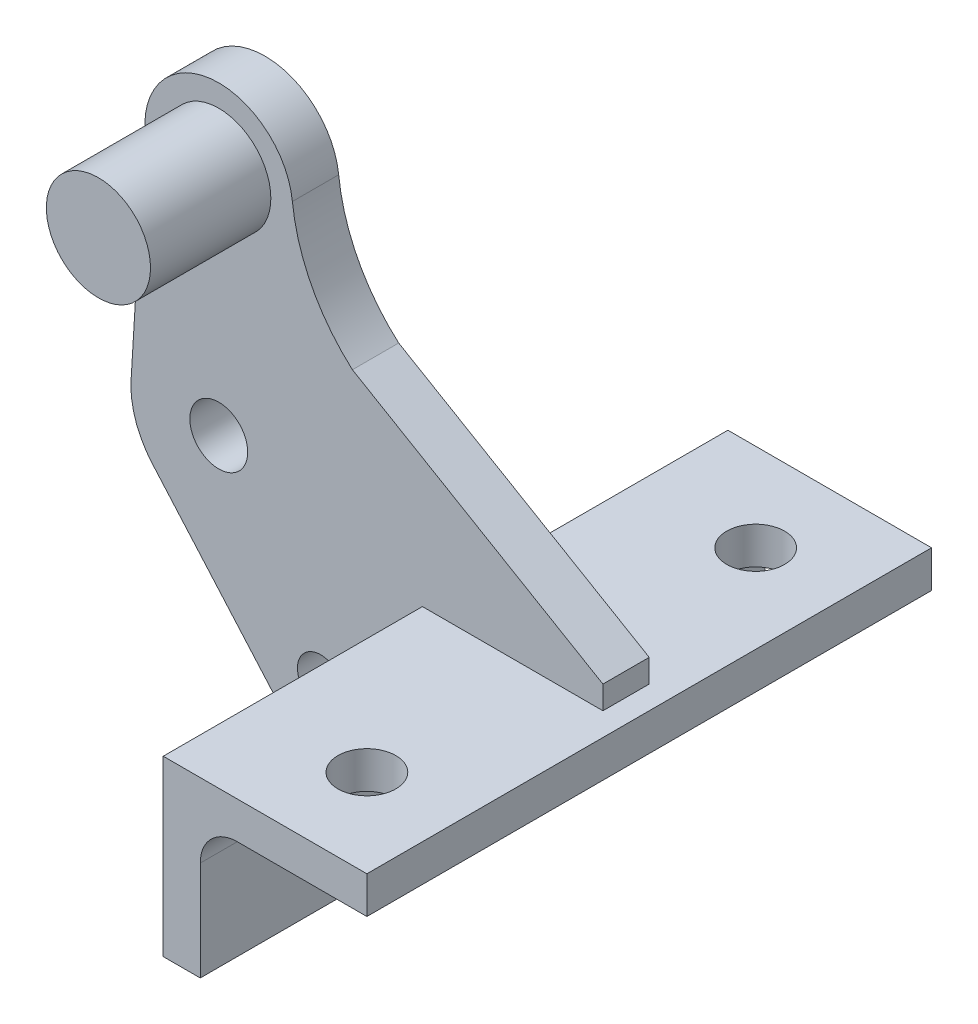
SolidWorks part; units mm, degrees
ref_plane "Front Plane" through (0, 0, 0) normal (0, 0, 1) x (1, 0, 0)
ref_plane "Top Plane" through (0, 0, 0) normal (0, 1, 0) x (1, 0, 0)
ref_plane "Right Plane" through (0, 0, 0) normal (1, 0, 0) x (0, 0, -1)
sketch "Sketch2" plane through (0, 0, 0) normal (0, 0, 1) x (1, 0, 0)
  line L0 (0, 0) -> (-44, 0)
  line L1 (-116.2541, 69.5893) -> (-62.5882, 8.2824)
  line L2 (-62.5882, 8.2824) -> (-63.9524, 8.3385)
  line L3 (78, 75) -> (78, 85)
  line L4 (-126, 95) -> (-119.6601, 199.6517)
  line L5 (78, 85) -> (78, 75)
  line L6 (0, 0) -> (0, 75)
  line L7 (0, 75) -> (78, 75)
  line L8 (-30.2464, 148.498) -> (78, 85)
  circle A0 centre (-44, 25) radius 10
  circle A1 centre (-44, 25) radius 10
  circle A2 centre (-88, 95) radius 12.5
  arc A4 (-44, 0) -> (-62.5882, 8.2824) centre (-44, 25) cw
  arc A5 (-116.2541, 69.5893) -> (-126, 95) centre (-88, 95) cw
  arc A6 (-119.6601, 199.6517) -> (-56.191, 198.4909) centre (-88, 195) cw
  arc A7 (-56.191, 198.4909) -> (-30.2464, 148.498) centre (21.3435, 207) ccw
  dimension "D3" = 25
  dimension "D4" = 20
  dimension "D5" = 44
  dimension "D7" = 25
  dimension "D9" = 38
  dimension "D10" = 78
  dimension "D14" = 100
  dimension "D16" = 32
  dimension "D6" = 70
  dimension "D8" = 44
  dimension "D13" = 10
  dimension "D15" = 12
sketch "Sketch3" plane through (0, 0, 0) normal (0, 0, 1) x (1, 0, 0)
  line L0 (0, 0) -> (0, 75)
  line L1 (0, 75) -> (78, 75)
  line L2 (78, 75) -> (88, 75)
  line L3 (88, 75) -> (88, 59)
  line L4 (88, 59) -> (32, 59)
  line L5 (16, 43) -> (16, 0)
  line L6 (16, 0) -> (0, 0)
  arc A0 (32, 59) -> (16, 43) centre (32, 43) ccw
  dimension "D6" = 16
  dimension "D1" = 75
  dimension "D2" = 78
  dimension "D3" = 88
  dimension "D4" = 16
  dimension "D5" = 16
sketch "Sketch5" plane through (0, 0, 0) normal (0, 0, 1) x (1, 0, 0)
sketch "Sketch8" plane through (0, 0, 0) normal (0, 0, 1) x (1, 0, 0)
  circle A0 centre (-88, 195) radius 22.5
  dimension "D1" = 45
extrude "Boss-Extrude14" add sketch "Sketch8" along normal blind 62
extrude "Boss-Extrude15" add sketch "Sketch2" along normal blind 10 and the other way blind 10 contours A7 A6 L4 A5 L1 A4 L0 L6 L7 L3 L8 A2 A0 region at (-52.3406, 106.4931, 0)
extrude "Boss-Extrude16" add sketch "Sketch3" along normal blind 122 and the other way blind 122
sketch "Sketch9" plane through (0, 75, 0) normal (0, 1, 0) x (1, 0, 0)
  line L0 (88, -122) -> (0, -122) construction
  line L1 (0, -10) -> (0, -122) construction
  line L2 (88, 122) -> (0, 122) construction
  line L3 (0, 122) -> (0, 10) construction
  circle A0 centre (50, -84) radius 12.5
  circle A1 centre (50, 84) radius 12.5
  dimension "D1" = 25
  dimension "D4" = 25
  dimension "D2" = 38
  dimension "D3" = 50
  dimension "D5" = 38
  dimension "D6" = 50
extrude "Cut-Extrude1" cut sketch "Sketch9" against normal blind 16
